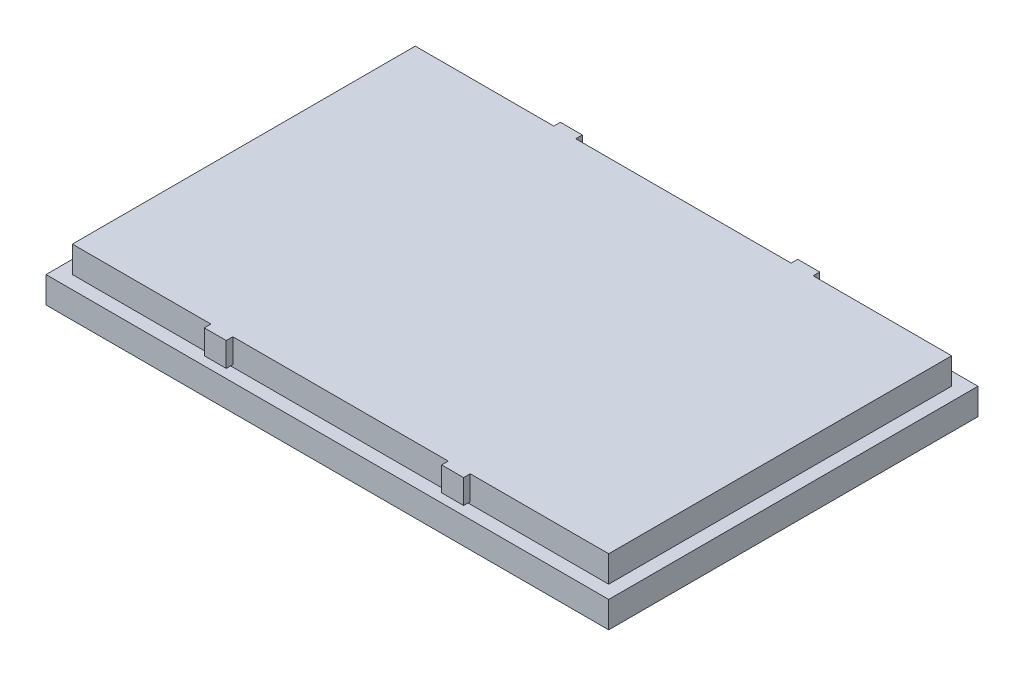
SolidWorks part; units mm, degrees
ref_plane "Front Plane" through (0, 0, 0) normal (0, 0, 1) x (1, 0, 0)
ref_plane "Top Plane" through (0, 0, 0) normal (0, 1, 0) x (1, 0, 0)
ref_plane "Right Plane" through (0, 0, 0) normal (1, 0, 0) x (0, 0, -1)
sketch "Sketch1" plane through (0, 0, 0) normal (0, 0, 1) x (1, 0, 0)
  line L1 (-39.6, 0) -> (-14, 0)
  line L2 (-39.6, 0) -> (-39.6, 1.2)
  line L3 (-39.6, 1.2) -> (-14, 1.2)
  line L4 (-14, 0) -> (-14, 1.2)
extrude "Boss-Extrude1" add sketch "Sketch1" along normal blind 16.8 from offset 72.4 offset against normal yes
sketch "Sketch2" plane through (0, 0, 0) normal (0, 0, 1) x (1, 0, 0)
  line L1 (-39, 1.19) -> (-14.6, 1.19)
  line L2 (-39, 1.19) -> (-39, 2.4)
  line L3 (-39, 2.4) -> (-14.6, 2.4)
  line L4 (-14.6, 1.19) -> (-14.6, 2.4)
extrude "Boss-Extrude2" add sketch "Sketch2" along normal blind 15.6 from offset 71.8 offset against normal yes
sketch "Sketch3" plane through (0, 0, 0) normal (0, 0, 1) x (1, 0, 0)
  line L1 (-21.9, 1.3) -> (-20.9, 1.3)
  line L2 (-21.9, 1.3) -> (-21.9, 2.4)
  line L3 (-21.9, 2.4) -> (-20.9, 2.4)
  line L4 (-20.9, 1.3) -> (-20.9, 2.4)
extrude "Boss-Extrude3" add sketch "Sketch3" along normal blind 0.31 from offset 72.1 offset against normal yes
sketch "Sketch4" plane through (0, 0, 0) normal (0, 0, 1) x (1, 0, 0)
  line L1 (-21.9, 1.3) -> (-20.9, 1.3)
  line L2 (-21.9, 1.3) -> (-21.9, 2.4)
  line L3 (-21.9, 2.4) -> (-20.9, 2.4)
  line L4 (-20.9, 1.3) -> (-20.9, 2.4)
extrude "Boss-Extrude4" add sketch "Sketch4" along normal blind 0.31 from offset 56.21 offset against normal yes
sketch "Sketch5" plane through (0, 0, 0) normal (0, 0, 1) x (1, 0, 0)
  line L1 (-32.7, 1.3) -> (-31.7, 1.3)
  line L2 (-32.7, 1.3) -> (-32.7, 2.4)
  line L3 (-32.7, 2.4) -> (-31.7, 2.4)
  line L4 (-31.7, 1.3) -> (-31.7, 2.4)
extrude "Boss-Extrude5" add sketch "Sketch5" along normal blind 0.31 from offset 72.1 offset against normal yes
sketch "Sketch6" plane through (0, 0, 0) normal (0, 0, 1) x (1, 0, 0)
  line L1 (-32.7, 1.3) -> (-31.7, 1.3)
  line L2 (-32.7, 1.3) -> (-32.7, 2.4)
  line L3 (-32.7, 2.4) -> (-31.7, 2.4)
  line L4 (-31.7, 1.3) -> (-31.7, 2.4)
extrude "Boss-Extrude6" add sketch "Sketch6" along normal blind 0.31 from offset 56.21 offset against normal yes
sketch "Sketch7" plane through (0, 0, 0) normal (0, 0, 1) x (1, 0, 0)
  line L1 (-28.3, -0.1) -> (-25.3, -0.1)
  line L2 (-28.3, -0.1) -> (-28.3, 0.6)
  line L3 (-28.3, 0.6) -> (-25.3, 0.6)
  line L4 (-25.3, -0.1) -> (-25.3, 0.6)
extrude "Boss-Extrude7" add sketch "Sketch7" along normal blind 0.9 from offset 72.5 separate body offset against normal yes
combine bodies "Combine1" operation type subtract main body 106 bodies to subtract 107
